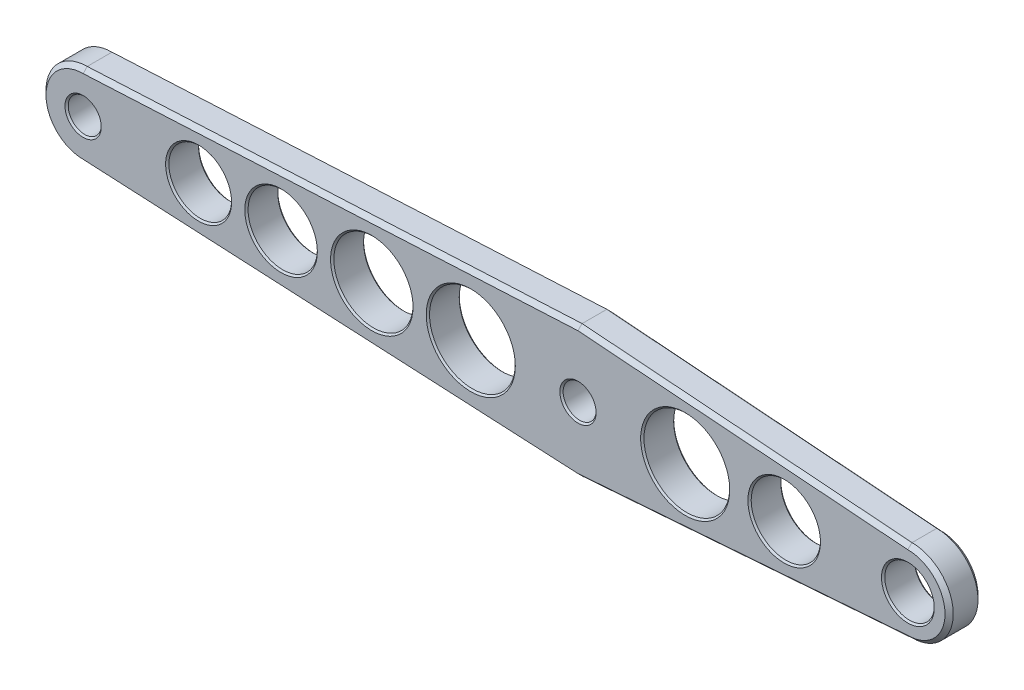
SolidWorks part; units mm, degrees
material "Copper"
ref_plane "Front Plane" through (0, 0, 0) normal (0, 0, 1) x (1, 0, 0)
ref_plane "Top Plane" through (0, 0, 0) normal (0, 1, 0) x (1, 0, 0)
ref_plane "Right Plane" through (0, 0, 0) normal (1, 0, 0) x (0, 0, -1)
sketch "Sketch1" plane through (0, 0, 0) normal (0, 0, 1) x (1, 0, 0)
  line L2 (-25, -2.5) -> (5, -4)
  line L4 (-25, 2.5) -> (5, 4)
  line L5 (5, 4) -> (25, 2.5)
  line L6 (5, -4) -> (25, -2.5)
  arc A0 (-25, -2.5) -> (-25, 2.5) centre (-25, 0) cw
  arc A2 (25, 2.5) -> (25, -2.5) centre (25, 0) cw
  circle A6 centre (-25, 0) radius 1
  circle A7 centre (-18, 0) radius 1.9
  circle A8 centre (-13, 0) radius 2.1
  circle A9 centre (-7.5, 0) radius 2.4
  circle A10 centre (-1.5, 0) radius 2.6
  circle A11 centre (5, 0) radius 1
  circle A12 centre (11.5, 0) radius 2.6
  circle A13 centre (17.5, 0) radius 2.1
  circle A14 centre (25, 0) radius 1.5
  point P4 (0, 0)
  point P8 (-25, 0)
  point P14 (25, 0)
  dimension "D3" = 2
  dimension "D6" = 3.8
  dimension "D7" = 4.2
  dimension "D8" = 4.8
  dimension "D9" = 5.2
  dimension "D14" = 2
  dimension "D15" = 5.2
  dimension "D16" = 4.2
  dimension "D17" = 3
  dimension "D19" = 7.5
  dimension "D1" = 50
  dimension "D2" = 5
  dimension "D4" = 5
  dimension "D10" = 7
  dimension "D11" = 5
  dimension "D12" = 5.5
  dimension "D13" = 6
  dimension "D18" = 30
  dimension "D20" = 6
extrude "Boss-Extrude1" add sketch "Sketch1" along normal blind 2
chamfer "Chamfer1" distance 0.25 angle 45 4 edges at (27.5, 0, 0) (27.5, 0, 2) (-27.5, 0, 0) (-27.5, 0, 2)
chamfer "Chamfer2" distance 0.1 angle 45 18 edges at (6, 0, 0) (6, 0, 2) (1.1, 0, 0) (1.1, 0, 2) (-5.1, 0, 0) (-5.1, 0, 2) (-10.9, 0, 0) (-10.9, 0, 2) (-16.1, 0, 0) (-16.1, 0, 2) (-24, 0, 0) (-24, 0, 2) (26.5, 0, 0) (26.5, 0, 2) (19.6, 0, 0) (19.6, 0, 2) (14.1, 0, 0) (14.1, 0, 2)
